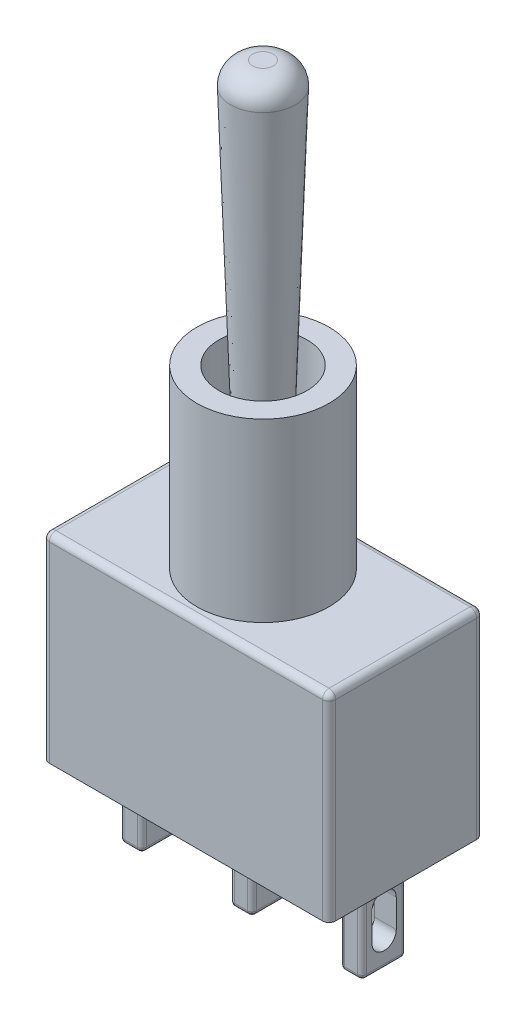
SolidWorks part; units mm, degrees
ref_plane "Front Plane" through (0, 0, 0) normal (0, 0, 1) x (1, 0, 0)
ref_plane "Top Plane" through (0, 0, 0) normal (0, 1, 0) x (1, 0, 0)
ref_plane "Right Plane" through (0, 0, 0) normal (1, 0, 0) x (0, 0, -1)
sketch "Sketch1" plane through (0, 0, 0) normal (0, 1, 0) x (1, 0, 0)
  line L0 (0, 3.5) -> (0, -3.5) construction
  line L1 (-6.5, 3.5) -> (6.5, 3.5)
  line L2 (-6.5, 3.5) -> (-6.5, -3.5)
  line L3 (-6.5, -3.5) -> (6.5, -3.5)
  line L4 (6.5, 3.5) -> (6.5, -3.5)
  line L5 (-6.5, 3.5) -> (6.5, -3.5) construction
  line L6 (-6.5, -3.5) -> (6.5, 3.5) construction
  line L7 (-0.5, 1) -> (0.5, 1)
  line L8 (-0.5, 1) -> (-0.5, -1)
  line L9 (-0.5, -1) -> (0.5, -1)
  line L10 (0.5, 1) -> (0.5, -1)
  line L11 (-0.5, 1) -> (0.5, -1) construction
  line L12 (-0.5, -1) -> (0.5, 1) construction
  line L13 (5.5, 1) -> (5.5, -1)
  line L14 (-5.5, 1) -> (-4.5, 1)
  line L15 (-5.5, 1) -> (-5.5, -1)
  line L16 (-5.5, -1) -> (-4.5, -1)
  line L17 (-4.5, 1) -> (-4.5, -1)
  line L18 (-5.5, 1) -> (-4.5, -1) construction
  line L19 (-5.5, -1) -> (-4.5, 1) construction
  line L20 (5.5, 1) -> (4.5, -1) construction
  line L21 (5.5, -1) -> (4.5, 1) construction
  line L22 (5.5, 1) -> (4.5, 1)
  line L23 (4.5, 1) -> (4.5, -1)
  line L24 (5.5, -1) -> (4.5, -1)
  point P0 (0, 0)
  point P6 (0, 0)
  point P13 (-5, 0)
  point P22 (5, 0)
  dimension "D1" = 13
  dimension "D2" = 7
  dimension "D3" = 1
  dimension "2" = 2
  dimension "D4" = 5
extrude "Boss-Extrude1" add sketch "Sketch1" along normal blind 9 contours L4 L1 L2 L3 L7 L10 L9 L8 L14 L17 L16 L15 L13 L24 L23 L22 | L17 L14 L15 L16 | L10 L7 L8 L9 | L24 L13 L22 L23 region at (0, 0, -3.3524) region at (0, 0, 0) region at (5, 0, 0) region at (-5, 0, 0)
extrude "Boss-Extrude2" add sketch "Sketch1<3>" against normal blind 4 contours L17 L14 L15 L16 | L10 L7 L8 L9 | L24 L13 L22 L23 region at (0, 0, 0) region at (5, 0, 0) region at (-5, 0, 0)
sketch "Sketch1<3>" plane through (0, 0, 0) normal (0, 1, 0) x (1, 0, 0) same geometry as "Sketch1"
sketch "Sketch2" plane through (0, 9, 0) normal (0, 1, 0) x (1, 0, 0)
  line L0 (-6.5, 3.5) -> (6.5, -3.5) construction
  line L1 (6.5, 3.5) -> (-6.5, -3.5) construction
  circle A0 centre (0, 0) radius 3
  circle A1 centre (0, 0) radius 2
  dimension "D1" = 6
  dimension "D2" = 4
extrude "Boss-Extrude3" add sketch "Sketch2" along normal blind 8
extrude "Boss-Extrude4" add sketch "Sketch2<6>" along normal blind 5 contours A1 region at (0, 9, 0)
sketch "Sketch2<6>" plane through (0, 9, 0) normal (0, 1, 0) x (1, 0, 0) same geometry as "Sketch2"
ref_plane "Plane1" through (0, 29, 0) normal (0, 1, 0) x (1, 0, 0)
sketch "Sketch3" plane through (0, 29, 0) normal (0, 1, 0) x (1, 0, 0)
  circle A0 centre (0, 0) radius 1.5
  dimension "D1" = 3
sketch "Sketch4" plane through (0, 14, 0) normal (0, 1, 0) x (1, 0, 0)
  circle A0 centre (0, 0) radius 1
  dimension "D1" = 2
loft "Loft1" add profiles "Sketch4", "Sketch3" start constraint default connector at (0.1397, 14, -0.9902) connector at (0.0666, 29, -1.4985)
fillet "Fillet1" radius 1 1 edges at (0, 29, 1.5)
sketch "Sketch5" plane through (-5.5, 0, 0) normal (-1, 0, 0) x (0, 0, 1)
  line L0 (0, -1.4337) -> (0, -2.7171) construction
  line L1 (0.55, -1.4337) -> (0.55, -2.7171)
  line L2 (-0.55, -1.4337) -> (-0.55, -2.7171)
  arc A0 (0.55, -1.4337) -> (-0.55, -1.4337) centre (0, -1.4337) ccw
  arc A1 (-0.55, -2.7171) -> (0.55, -2.7171) centre (0, -2.7171) ccw
  point P3 (0, -2.0754)
extrude "Cut-Extrude1" cut sketch "Sketch5" against normal blind 12 contours L1 A1 L2 A0
fillet "Fillet2" radius 0.3 8 edges at (6.5, 4.5, -3.5) (-6.5, 4.5, -3.5) (-6.5, 9, 0) (6.5, 4.5, 3.5) (0, 9, 3.5) (-6.5, 4.5, 3.5) (0, 9, -3.5) (6.5, 9, 0)
fillet "Fillet3" radius 0.2 24 edges at (-4.5, -2, 1) (-5.5, -2, 1) (-5.5, -4, 0) (-5, -4, 1) (-4.5, -4, 0) (-5, -4, -1) (-4.5, -2, -1) (-5.5, -2, -1) (0.5, -2, 1) (0.5, -4, 0) (0, -4, 1) (5, -4, 1) (5, -4, -1) (0, -4, -1) (0.5, -2, -1) (-0.5, -2, 1) (-0.5, -4, 0) (-0.5, -2, -1) (4.5, -2, 1) (4.5, -4, 0) (4.5, -2, -1) (5.5, -2, 1) (5.5, -4, 0) (5.5, -2, -1)
